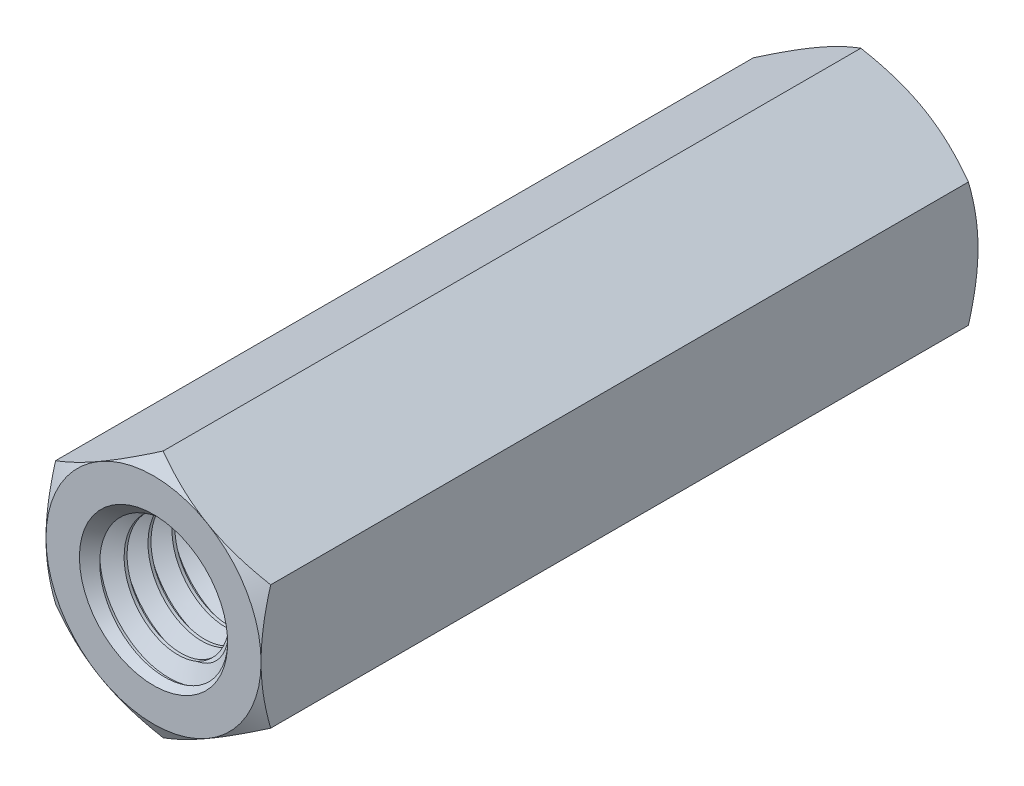
SolidWorks part; units mm, degrees
ref_plane "Front Plane" through (0, 0, 0) normal (0, 0, 1) x (1, 0, 0)
ref_plane "Top Plane" through (0, 0, 0) normal (0, 1, 0) x (1, 0, 0)
ref_plane "Right Plane" through (0, 0, 0) normal (1, 0, 0) x (0, 0, -1)
sketch "Sketch3" plane through (0, 0, 0) normal (1, 0, 0) x (0, 0, -1)
  line L0 (-7.5, 0) -> (7.5, 0) construction
  line L1 (0, 2.25) -> (0, -2.25) construction
  line L2 (-7.5, 1.5) -> (-7.5, -1.5) construction
  point P2 (1.5, 0)
  point P3 (-1.5, 0)
  dimension "Length" = 15
  dimension "Min Thread Length" = 6
  dimension "D1" = 6
  dimension "Thread Dia" = 3
  dimension "Hex" = 4.5
sketch "Sketch1" plane through (0, 0, 0) normal (0, 0, 1) x (1, 0, 0)
  line L1 (0, 2.5981) -> (-2.25, 1.299)
  line L2 (-2.25, 1.299) -> (-2.25, -1.299)
  line L3 (-2.25, -1.299) -> (0, -2.5981)
  line L4 (0, -2.5981) -> (2.25, -1.299)
  line L5 (2.25, -1.299) -> (2.25, 1.299)
  line L6 (2.25, 1.299) -> (0, 2.5981)
  circle A0 centre (0, 0) radius 2.25 construction
  circle A1 centre (0, 0) radius 1.5
extrude "Extrude1" add sketch "Sketch1" along normal up to vertex (7.5 mm away) and the other way up to vertex (7.5 mm away) up to point (0, 0, 7.5) other way up to point (0, 0, -7.5)
sketch "Sketch11" plane through (0, 0, -7.5) normal (0, 0, -1) x (-1, 0, 0)
  circle A0 centre (0, 0) radius 1.5 construction
  circle A1 centre (0, 0) radius 1.5
curve "Helix/Spiral1" pitch 0.5 height 15.5 radius 1.5 centre (0, 0, -7.5) axis (0, 0, 1) start towards (0, 1, 0) parameters "Pitch"=0.5
sketch "Sketch12" plane through (0, 0, 0) normal (1, 0, 0) x (0, 0, -1)
  line L0 (7.9375, 1.5) -> (7.5, 1.5)
  line L1 (7.9375, 1.5) -> (7.75, 1.1752)
  line L2 (7.75, 1.1752) -> (7.6875, 1.1752)
  line L3 (7.6875, 1.1752) -> (7.5, 1.5)
  line L4 (7.7188, 1.1752) -> (7.7188, 1.5) construction
  line L5 (7.8438, 1.3376) -> (7.5938, 1.3376) construction
  dimension "D1" = 0.0625
  dimension "D2" = 0.25
  dimension "D3" = 60
sweep "Sweep1" add profiles "Sketch12" path "Helix/Spiral1"
sketch "Sketch6" plane through (0, 0, -7.5) normal (0, 0, -1) x (-1, 0, 0)
  line L6 (0, 2.5981) -> (-2.25, 1.299)
  line L7 (-2.25, 1.299) -> (-2.25, -1.299)
  line L8 (-2.25, -1.299) -> (0, -2.5981)
  line L9 (0, -2.5981) -> (2.25, -1.299)
  line L10 (2.25, -1.299) -> (2.25, 1.299)
  line L11 (2.25, 1.299) -> (0, 2.5981)
  line L12 (0, 2.5981) -> (-2.25, 1.299)
  line L13 (-2.25, 1.299) -> (-2.25, -1.299)
  line L14 (-2.25, -1.299) -> (0, -2.5981)
  line L15 (0, -2.5981) -> (2.25, -1.299)
  line L16 (2.25, -1.299) -> (2.25, 1.299)
  line L17 (2.25, 1.299) -> (0, 2.5981)
  dimension "D1" = 0
extrude "Extrude2" cut sketch "Sketch6" along normal through all
sketch "Sketch7" plane through (0, 0, -7.5) normal (0, 0, -1) x (-1, 0, 0)
  circle A2 centre (0, 0) radius 1.5508
  circle A3 centre (0, 0) radius 1.5508
  dimension "D1" = 0.0508
extrude "Extrude3" cut sketch "Sketch7" against normal through all draft 43
sketch "Sketch8" plane through (0, 0, -7.5) normal (0, 0, -1) x (-1, 0, 0)
  circle A0 centre (0, 0) radius 2.25 construction
  circle A1 centre (0, 0) radius 2.25
extrude "Extrude4" cut sketch "Sketch8" against normal through all draft 60 flip side to cut
mirror "Mirror1" about plane through (0, 0, 0) normal (0, 0, 1) of "Extrude2", "Extrude3", "Extrude4"
sketch "Sketch9" plane through (0, 0, 0) normal (1, 0, 0) x (0, 0, -1)
  line L1 (-1.5, 1.5508) -> (1.5, 1.5508)
  line L2 (-1.5, 1.5508) -> (-1.5, 0)
  line L3 (-1.5, 0) -> (1.5, 0)
  line L4 (1.5, 1.5508) -> (1.5, 0)
  line L7 (-7.5, 0) -> (7.5, 0) construction
revolve "Revolve" add sketch "Sketch9" angle 360 about L0
sketch "Sketch10" plane through (0, 0, 0) normal (1, 0, 0) x (0, 0, -1)
  line L0 (7.5, 1.5) -> (1.5, 1.5)
  line L1 (-7.5, 1.5) -> (-1.5, 1.5)
  line L2 (1.5, 1.5) -> (1.5, -1.5)
  line L3 (-7.5, -1.5508) -> (-1.5, -1.5508)
  line L4 (-1.5, 1.5) -> (-1.5, -1.5508)
  line L5 (1.5, -1.5) -> (7.5, -1.5)
sketch "Sketch13" plane through (0, 0, 7.5) normal (0, 0, 1) x (1, 0, 0)
  line L0 (0, 0) -> (1.1752, 0) construction
  line L1 (0, 0) -> (0.831, 0.831) construction
  line L2 (0, 0) -> (0.831, -0.831) construction
  arc A0 (0.5013, -1.063) -> (1.1082, -0.3912) centre (0, 0) ccw construction
  arc A1 (-0.8234, -0.8386) -> (0, -1.1752) centre (0, 0) ccw construction
  dimension "D1" = 45
  dimension "D2" = 45
equation "\"D1@Sketch3\" = \"Min Thread Length@Sketch3\""
equation "\"D3@Helix/Spiral1\" = \"Length@Sketch3\"+\"Pitch@Helix/Spiral1\""
equation "\"D1@Sketch12\" = \"Pitch@Helix/Spiral1\"*.125"
equation "\"D2@Sketch12\" = \"Pitch@Helix/Spiral1\"*.5"
